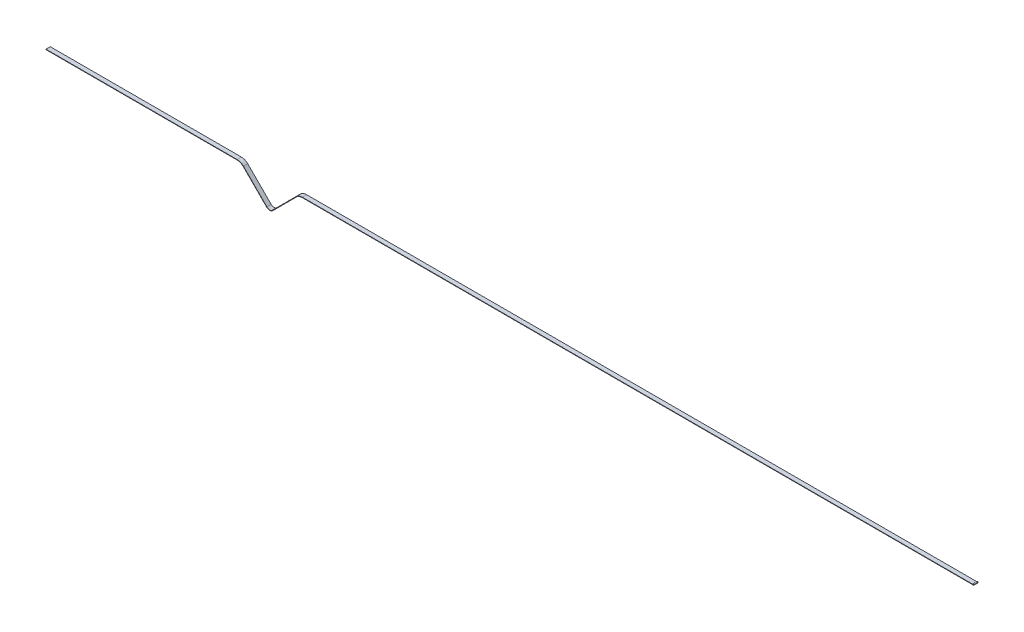
SolidWorks part; units mm, degrees
ref_plane "Front Plane" through (0, 0, 0) normal (0, 0, 1) x (1, 0, 0)
ref_plane "Top Plane" through (0, 0, 0) normal (0, 1, 0) x (1, 0, 0)
ref_plane "Right Plane" through (0, 0, 0) normal (1, 0, 0) x (0, 0, -1)
sketch "Sketch1" plane through (0, 0, 0) normal (1, 0, 0) x (0, 0, -1)
  line L1 (0, 0) -> (6, 0)
  line L2 (0, 0) -> (0, 0.63)
  line L3 (0, 0.63) -> (6, 0.63)
  line L4 (6, 0) -> (6, 0.63)
  dimension "D1" = 0.63
  dimension "D2" = 6
sketch "Sketch2" plane through (0, 0, 0) normal (0, 0, 1) x (1, 0, 0)
  line L0 (0, 0) -> (-937.7651, 0)
  line L1 (-946.2202, -3.5053) -> (-979.012, -36.3377)
  line L2 (-987.6582, -36.3377) -> (-1020.4499, -3.5053)
  line L3 (-1028.9051, 0) -> (-1295.84, 0)
  arc A0 (-937.7651, 0) -> (-946.2202, -3.5053) centre (-937.7651, -11.95) ccw
  arc A1 (-979.012, -36.3377) -> (-987.6582, -36.3377) centre (-983.3351, -32.02) cw
  arc A2 (-1020.4499, -3.5053) -> (-1028.9051, 0) centre (-1028.9051, -11.95) ccw
  dimension "D1" = 6.11
  dimension "D4" = 1295.84
sweep "Sweep1" add profiles "Sketch1" path "Sketch2"
sketch "Sketch3" plane through (0, 0, 0) normal (0, 0, 1) x (1, 0, 0)
  line L0 (0, 0.63) -> (-937.7651, 0.63) construction
  line L1 (-1.5, 0.63) -> (-1.5, 0)
  line L2 (0, 0) -> (-937.7651, 0) construction
  line L3 (-1.5, 0) -> (0, 0)
  line L4 (0, 0) -> (0, 0.63)
  arc A1 (0, 0.63) -> (-1.5, 0.63) centre (-0.75, 0.63) ccw
  dimension "D1" = 0.75
extrude "Boss-Extrude1" add sketch "Sketch3" against normal through all
pattern_curve "CrvPattern1" [suppressed] of bodies 102 driven by "Sketch2" parameters "D1"=2000, "D3"=2, "D2"=1, "D4"=10
